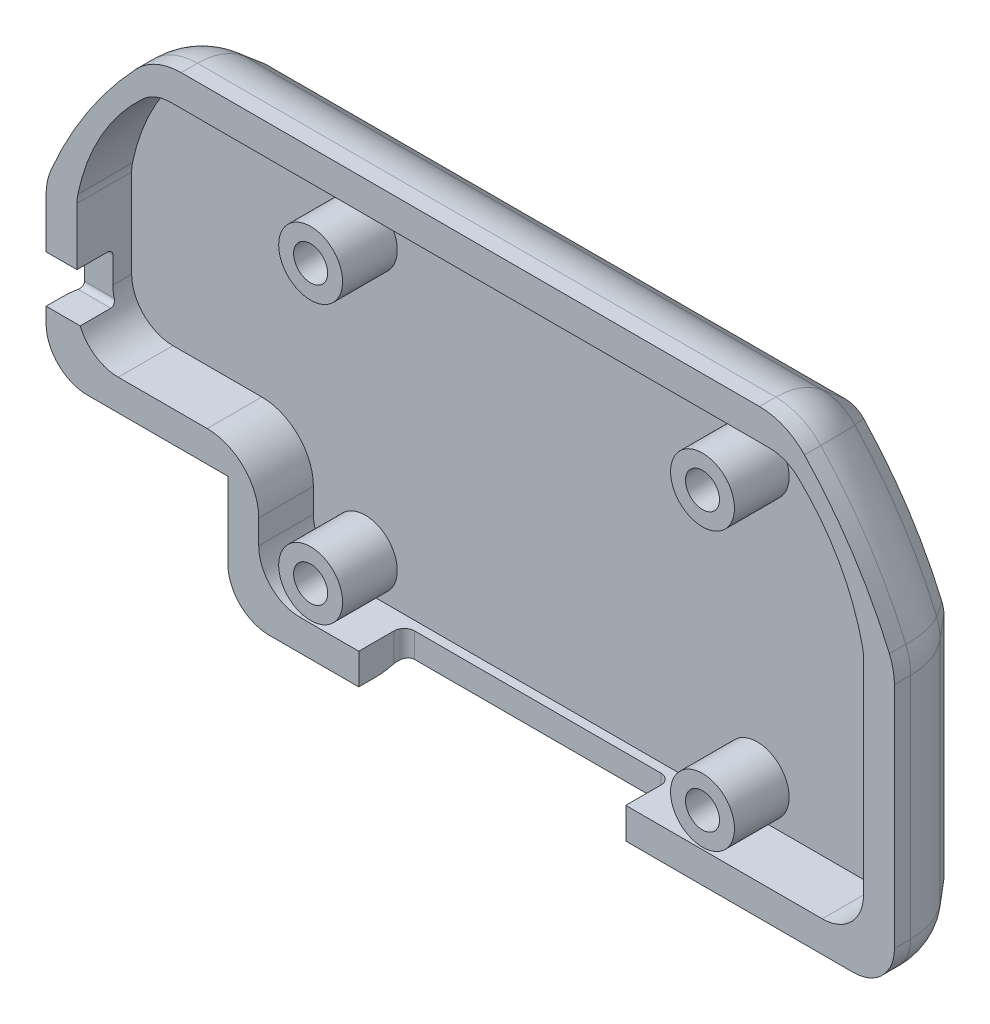
SolidWorks part; units mm, degrees
ref_plane "Alzado" through (0, 0, 0) normal (0, 0, 1) x (1, 0, 0)
ref_plane "Planta" through (0, 0, 0) normal (0, 1, 0) x (1, 0, 0)
ref_plane "Vista lateral" through (0, 0, 0) normal (1, 0, 0) x (0, 0, -1)
sketch "Croquis2" plane through (0, 0, 0) normal (0, 0, 1) x (1, 0, 0)
  line L0 (-43.6, 25.3285) -> (-43.6, 41.313)
  line L1 (-32.9688, 56.9561) -> (28.051, 56.9561)
  line L2 (38.6624, 41.313) -> (38.6624, 25.3285)
  line L7 (-43.6, 25.3285) -> (-25.98, 25.3285)
  line L8 (-25.98, 25.3285) -> (-25.98, 13.9787)
  line L9 (-25.98, 13.9787) -> (38.6624, 13.9787)
  line L10 (38.6624, 13.9787) -> (38.6624, 25.3285)
  arc A0 (-43.6, 41.313) -> (-32.9688, 56.9561) centre (-3.7394, 25.6575) cw
  arc A1 (28.051, 56.9561) -> (38.6624, 41.313) centre (-1.2097, 25.6867) cw
extrude "Saliente-Extruir1" add sketch "Croquis2" along normal blind 8.3
sketch "Croquis3" plane through (0, 0, 8.3) normal (0, 0, 1) x (1, 0, 0)
  line L0 (35.6624, 41.313) -> (35.6624, 28.3285)
  line L1 (-40.6, 28.3285) -> (-22.98, 28.3285)
  line L2 (-40.6, 41.313) -> (-40.6, 28.3285)
  line L7 (-22.98, 28.3285) -> (-22.98, 16.9787)
  line L8 (-22.98, 16.9787) -> (35.6624, 16.9787)
  line L11 (35.6624, 16.9787) -> (35.6624, 28.3285)
  line L17 (-32.9688, 53.9561) -> (28.0724, 53.9561)
  arc A0 (-40.6, 41.313) -> (-32.9688, 53.9561) centre (-19.994, 37.5001) cw
  arc A1 (28.0724, 53.9561) -> (35.6624, 41.313) centre (14.5103, 37.2147) cw
  point P1 (0, 0)
  point P7 (0, 0)
  point P8 (0, 0)
  point P12 (0, 0)
extrude "Cortar-Extruir1" cut sketch "Croquis3" against normal blind 5.3
fillet "Redondeo1" radius 4 10 edges at (35.6624, 16.9787, 5.65) (35.6624, 41.313, 5.65) (28.0724, 53.9561, 5.65) (-22.98, 16.9787, 5.65) (-40.6, 28.3285, 5.65) (-32.9688, 53.9561, 5.65) (-40.6, 41.313, 5.65) (38.6624, 13.9787, 4.15) (-25.98, 13.9787, 4.15) (-43.6, 25.3285, 4.15)
fillet "Redondeo2" radius 6 4 edges at (-43.6, 41.313, 4.15) (-32.9688, 56.9561, 4.15) (38.6624, 41.313, 4.15) (28.051, 56.9561, 4.15)
chamfer "Chaflán1" distance 3.5 angle 50 15 edges at (27.9535, 56.4654, 0) (-2.4607, 56.9561, 0) (-32.872, 56.4667, 0) (-39.5452, 49.1503, 0) (-43.478, 41.3361, 0) (-43.6, 34.7305, 0) (-42.4285, 26.5001, 0) (-32.79, 25.3285, 0) (-25.98, 21.6536, 0) (-24.8085, 15.1503, 0) (6.3412, 13.9787, 0) (37.4908, 15.1503, 0) (38.6624, 29.0568, 0) (38.5409, 41.3362, 0) (34.6182, 49.1458, 0) first distance on face at (-6.9571, 35.4937, 0)
fillet "Redondeo3" radius 7 15 edges at (-42.4285, 26.5001, 4.1711) (-24.8085, 15.1503, 4.1711) (-32.79, 25.3285, 4.1711) (-25.98, 21.6536, 4.1711) (-43.6, 34.7305, 4.1711) (-43.478, 41.3361, 4.1711) (-39.5452, 49.1503, 4.1711) (-32.872, 56.4667, 4.1711) (27.9535, 56.4654, 4.1711) (-2.4607, 56.9561, 4.1711) (38.5409, 41.3362, 4.1711) (34.6182, 49.1458, 4.1711) (38.6624, 29.0568, 4.1711) (37.4908, 15.1503, 4.1711) (6.3412, 13.9787, 4.1711)
sketch "Croquis4" plane through (0, 0, 0) normal (0, 0, -1) x (-1, 0, 0)
  circle A8 centre (-20.0535, 20.2867) radius 2.775
  circle A10 centre (-20.0535, 47.1867) radius 2.775
  circle A11 centre (17.9465, 47.2217) radius 2.775
  circle A12 centre (17.9465, 20.3217) radius 2.755
  dimension "D2" = 26.9
extrude "Cortar-Extruir2" cut sketch "Croquis4" against normal blind 5
sketch "Croquis7" plane through (-23.5317, 0, -19.7454) normal (-0.766, 0, -0.6428) x (-0.6428, 0, 0.766)
sketch "Croquis8" plane through (-43.6, 0, 0) normal (-1, 0, 0) x (0, 0, 1)
  line L0 (8.6236, 35.3575) -> (8.6236, 30.7915)
  line L4 (4.8292, 35.3575) -> (4.8292, 30.7915)
  line L5 (4.8292, 30.7915) -> (8.6236, 30.7915)
  line L6 (8.6236, 35.3575) -> (4.8292, 35.3575)
extrude "Cortar-Extruir3" cut sketch "Croquis8" against normal blind 5
sketch "Croquis9" plane through (-25.98, 0, 0) normal (-1, 0, 0) x (0, 0, 1)
  line L0 (8.4088, 23.1178) -> (8.4088, 17.9733)
  line L1 (8.4088, 23.1178) -> (4.7271, 23.1178)
  line L2 (4.7271, 23.1178) -> (4.7935, 18.0212)
  line L3 (4.7935, 18.0212) -> (8.4088, 17.9733)
fillet "Redondeo8" radius 5 1 edges at (-22.98, 28.3285, 5.65)
sketch "Croquis12" plane through (0, 0, 3) normal (0, 0, 1) x (1, 0, 0)
  circle A1 centre (-17.9465, 47.2217) radius 3.1
  circle A2 centre (-17.9465, 47.2217) radius 1.65
  circle A3 centre (-17.9465, 20.3217) radius 1.65
  circle A4 centre (-17.9465, 20.3217) radius 3.1
  circle A5 centre (20.0535, 20.2867) radius 1.65
  circle A6 centre (20.0535, 20.2867) radius 3.1
  circle A7 centre (20.0535, 47.1867) radius 1.65
  circle A8 centre (20.0535, 47.1867) radius 3.1
  circle A10 centre (20.0535, 20.2867) radius 2.775 construction
  circle A11 centre (20.0535, 47.1867) radius 2.775 construction
  circle A14 centre (-17.9465, 47.2217) radius 2.775 construction
  circle A15 centre (-17.9465, 20.3217) radius 2.755 construction
extrude "Saliente-Extruir4" add sketch "Croquis12" along normal up to surface (5.3 mm away) up to face at (-10.4031, 35.2913, 8.3)
fillet "Redondeo9" radius 0.5 2 edges at (-41.8165, 30.7915, 4.8292) (-41.9701, 35.3575, 4.8292)
sketch "Croquis14" plane through (0, 16.9787, 0) normal (0, 1, 0) x (1, 0, 0)
  line L1 (-13.279, -9.379) -> (-13.2784, -3.8865)
  line L2 (-13.2784, -3.8865) -> (12.6103, -3.8865)
  line L3 (12.6103, -3.8865) -> (12.6103, -11.0043)
  line L4 (12.6103, -11.0043) -> (-13.279, -9.379)
extrude "Cortar-Extruir4" cut sketch "Croquis14" against normal blind 10
fillet "Redondeo10" radius 1 2 edges at (-13.2784, 15.7781, 3.8865) (12.6103, 15.7781, 3.8865)
